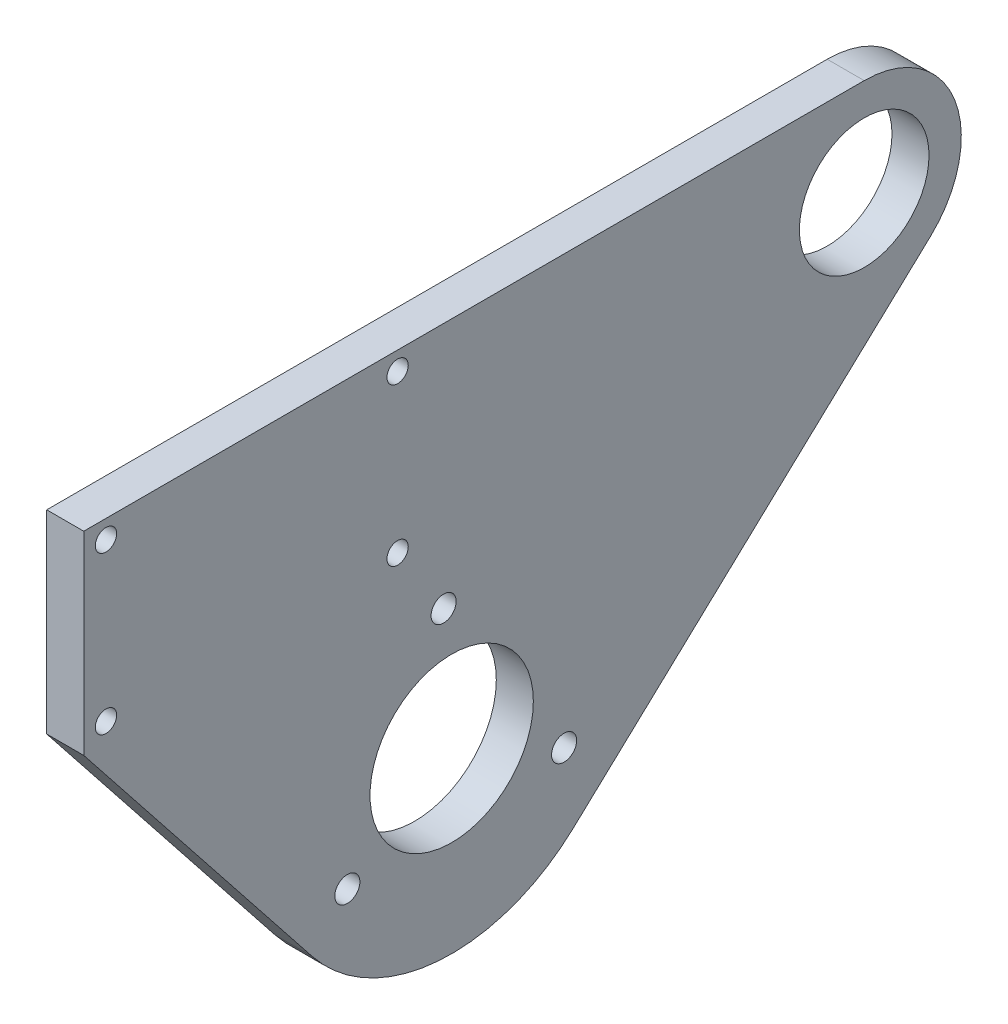
SolidWorks part; units mm, degrees
material "6061 Alloy"
ref_plane "Front Plane" through (0, 0, 0) normal (0, 0, 1) x (1, 0, 0)
ref_plane "Top Plane" through (0, 0, 0) normal (0, 1, 0) x (1, 0, 0)
ref_plane "Right Plane" through (0, 0, 0) normal (1, 0, 0) x (0, 0, -1)
sketch "Sketch1" plane through (0, 0, 0) normal (1, 0, 0) x (0, 0, -1)
  line L0 (-49.9001, -69.4268) -> (11.3662, -12.16)
  line L1 (-133.81, 16.645) -> (-76.19, 16.645)
  line L2 (-133.81, 16.645) -> (-133.81, -16.645)
  line L3 (-133.81, -16.645) -> (-76.19, -16.645)
  line L4 (-76.19, 16.645) -> (-76.19, -16.645)
  line L5 (-130, 13.475) -> (-80, 13.475)
  line L6 (-130, 13.475) -> (-130, -13.475)
  line L7 (-130, -13.475) -> (-80, -13.475)
  line L8 (-80, 13.475) -> (-80, -13.475)
  line L9 (-76.19, 16.645) -> (0, 16.645)
  line L10 (-133.81, -16.645) -> (-94.6322, -66.0872)
  circle A0 centre (0, 0) radius 11.1125
  circle A1 centre (-70.7273, -47.145) radius 14
  circle A2 centre (-70.7273, -47.145) radius 21.5 construction
  circle A3 centre (-70.7273, -47.145) radius 30.5
  circle A4 centre (0, 0) radius 16.645
  point P4 (-133.81, 0)
  point P12 (-130, 0)
  dimension "D6" = 22.225
  dimension "D7" = 28
  dimension "D8" = 43
  dimension "D9" = 61
  dimension "D11" = 0
  dimension "D1" = 33.29
  dimension "D2" = 80
  dimension "D3" = 26.95
  dimension "D4" = 50
  dimension "D5" = 3.81
  dimension "D10" = 85
  dimension "D12" = 3.81
extrude "Boss-Extrude1" add sketch "Sketch1" along normal mid plane 6.35 contours A3 A1 | A4 L9 L4 L3 A3 L0 | A4 A0 | L4 L1 L2 L3 L5 L8 L7 L6 | L8 L5 L6 L7 | A3 L3 L10 region at (0, -15.0674, 52.9598) region at (0, -76.7001, 72.9338) region at (0, -5.9367, 15.0453) region at (0, 0, 133.1445) region at (0, 0, 105)
hole_wizard "#6 Clearance Hole1" positions "Sketch2" profile "Sketch3" hole size "#6" standard "ANSI Inch" end condition up to next
sketch "Sketch2" plane through (3.175, 0, 0) normal (1, 0, 0) x (0, 0, -1)
  point P0 (-80, -13.475)
  point P3 (-80, 13.475)
  point P6 (-130, 13.475)
  point P9 (-130, -13.475)
sketch "Sketch3" plane through (3.175, -13.475, 80) normal (0, 1, 0) x (0, 0, -1)
  line L0 (0, 0) -> (0, 6.35)
  line L1 (0, 6.35) -> (1.8288, 6.35)
  line L2 (1.8288, 6.35) -> (1.8288, 0)
  line L5 (1.8288, 0) -> (0, 0)
  line L11 (0, -6.35) -> (0, 107.95) construction
  dimension "Thru Hole Dia." = 3.6576
  dimension "Thru Hole Depth" = 6.35
hole_wizard "M4 Clearance Hole1" positions "Sketch4" profile "Sketch5" hole size "M4" standard "ANSI Metric" end condition up to next
sketch "Sketch4" plane through (3.175, 0, 0) normal (1, 0, 0) x (0, 0, -1)
  line L0 (-69.5572, -46.365) -> (1.1701, 0.78) construction
  line L1 (-70.7273, -47.145) -> (-72.6883, -16.7081) construction
  line L3 (-70.7273, -47.145) -> (-43.3877, -60.6652) construction
  circle A0 centre (-70.7273, -47.145) radius 21.5 construction
  circle A1 centre (-70.7273, -47.145) radius 30.5 construction
  point P9 (-88.6171, -59.0699)
  point P26 (-51.4551, -56.6756)
  point P28 (-72.1096, -25.6895)
  dimension "D1" = 120
  dimension "D2" = 120
sketch "Sketch5" plane through (3.175, -25.6895, 72.1096) normal (0, 1, 0) x (0, 0, -1)
  line L0 (0, 0) -> (0, 6.35)
  line L1 (0, 6.35) -> (2.15, 6.35)
  line L2 (2.15, 6.35) -> (2.15, 0)
  line L5 (2.15, 0) -> (0, 0)
  line L11 (0, -6.35) -> (0, 107.95) construction
  dimension "Thru Hole Dia." = 4.3
  dimension "Thru Hole Depth" = 6.35
